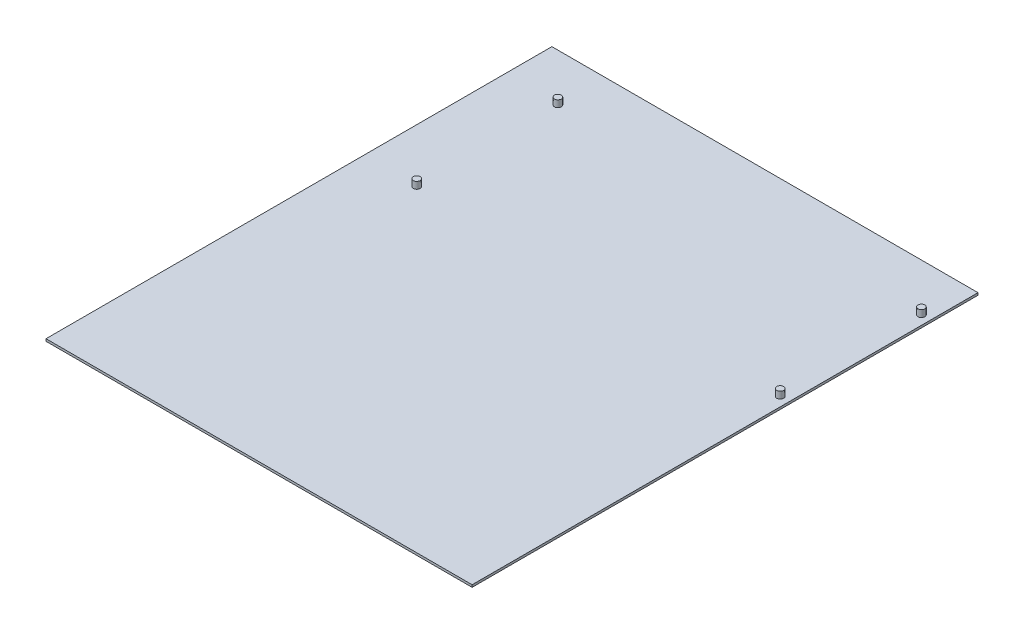
SolidWorks part; units mm, degrees
ref_plane "Front Plane" through (0, 0, 0) normal (0, 0, 1) x (1, 0, 0)
ref_plane "Top Plane" through (0, 0, 0) normal (0, 1, 0) x (1, 0, 0)
ref_plane "Right Plane" through (0, 0, 0) normal (1, 0, 0) x (0, 0, -1)
sketch "Sketch1" plane through (0, 0, 0) normal (0, 1, 0) x (1, 0, 0)
  line L1 (-56.1029, 186.4626) -> (130.8971, 186.4626)
  line L2 (-56.1029, 186.4626) -> (-56.1029, -35.5374)
  line L3 (-56.1029, -35.5374) -> (130.8971, -35.5374)
  line L4 (130.8971, 186.4626) -> (130.8971, -35.5374)
  dimension "D1" = 187
  dimension "D2" = 222
extrude "Boss-Extrude1" add sketch "Sketch1" along normal blind 1
sketch "Sketch2" plane through (0, 1, 0) normal (0, 1, 0) x (1, 0, 0)
  line L0 (130.8971, 186.4626) -> (-56.1029, 186.4626) construction
  line L2 (86.8971, 187.4626) -> (86.8971, 186.4626) construction
  circle A0 centre (126.8971, 165.6326) radius 1.5
  circle A1 centre (-32.6149, 165.6326) radius 1.5
  circle A2 centre (126.8971, 103.6566) radius 1.5
  circle A3 centre (-32.6149, 103.6526) radius 1.5
  dimension "D2" = 3
  dimension "D3" = 3
  dimension "D4" = 3
  dimension "D5" = 61.976
  dimension "D6" = 159.512
  dimension "D7" = 61.98
  dimension "D8" = 0
  dimension "D9" = 0
  dimension "D10" = 0
  dimension "D11" = 20.83
  dimension "D12" = 40
extrude "Boss-Extrude2" add sketch "Sketch2" along normal blind 3
